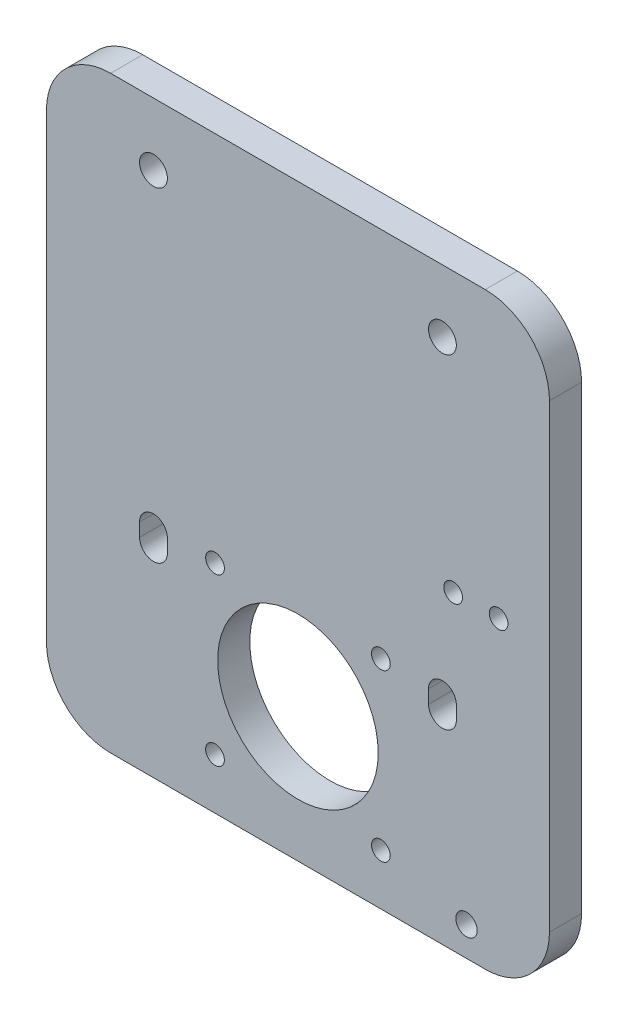
SolidWorks part; units mm, degrees
material "Polycarbonate (PC)"
ref_plane "Спереди" through (0, 0, 0) normal (0, 0, 1) x (1, 0, 0)
ref_plane "Сверху" through (0, 0, 0) normal (0, 1, 0) x (1, 0, 0)
ref_plane "Справа" through (0, 0, 0) normal (1, 0, 0) x (0, 0, -1)
sketch "Model" plane through (0, 0, 0) normal (0, 0, 1) x (1, 0, 0)
  line L4 (-22.7195, 98.3) -> (-31.6357, 98.3) construction
  line L5 (-27, 102.2644) -> (-27, 93.0751) construction
  line L24 (-27, 44.8397) -> (-27, 32.6753) construction
  line L25 (-29.6, 40.1) -> (-29.6, 37.6)
  line L26 (-24.4, 37.6) -> (-24.4, 40.1)
  line L27 (-24.4, 40.1) -> (-24.4, 37.6)
  line L28 (-29.6, 37.6) -> (-29.6, 40.1)
  line L156 (-18.8648, 25) -> (20.0371, 25) construction
  line L159 (27, 44.8397) -> (27, 32.6753) construction
  line L160 (47, 98) -> (47, 12)
  line L165 (27, 102.2644) -> (27, 93.0751) construction
  line L166 (22.7195, 98.3) -> (31.6357, 98.3) construction
  line L167 (35, 0) -> (-35, 0)
  line L174 (-47, 12) -> (-47, 98)
  line L181 (-35, 110) -> (35, 110)
  line L955 (29.6, 37.6) -> (29.6, 40.1)
  line L968 (24.4, 40.1) -> (24.4, 37.6)
  line L1360 (24.4, 37.6) -> (24.4, 40.1)
  line L1373 (29.6, 40.1) -> (29.6, 37.6)
  line L1604 (0, -6.1891) -> (0, 116.9068) construction
  arc A0 (35, 110) -> (47, 98) centre (35, 98) cw
  arc A1 (47, 12) -> (35, 0) centre (35, 12) cw
  arc A2 (-47, 12) -> (-35, 0) centre (-35, 12) ccw
  arc A3 (-47, 98) -> (-35, 110) centre (-35, 98) cw
  circle A8 centre (0, 25) radius 15
  arc A9 (24.4, 40.1) -> (29.6, 40.1) centre (27, 40.1) cw
  arc A10 (24.4, 37.6) -> (29.6, 37.6) centre (27, 37.6) ccw
  circle A19 centre (27, 98.3) radius 2.6
  circle A22 centre (-27, 98.3) radius 2.6
  arc A29 (-24.4, 37.6) -> (-29.6, 37.6) centre (-27, 37.6) cw
  arc A30 (-24.4, 40.1) -> (-29.6, 40.1) centre (-27, 40.1) ccw
  dimension "D1" = 12
  dimension "D12" = 30
  dimension "D15" = 2.6
  dimension "D38" = 5.2
  dimension "D3" = 110
  dimension "D4" = 25
  dimension "D6" = 40.1
  dimension "D7" = 94
  dimension "D8" = 54
  dimension "D13" = 5.2
  dimension "D14" = 2.5
  dimension "D36" = 58.2
extrude "Base" add sketch "Model" along normal blind 6 contours A3 L174 A2 L167 A1 L160 A0 L181 A30 L26 A29 L25 A8 A10 L968 A9 L955 region at (0, 57.1783, 0)
sketch "Sketch2" plane through (0, 0, 6) normal (0, 0, 1) x (1, 0, 0)
  line L0 (35, 0) -> (-35, 0) construction
  line L1 (47, 98) -> (47, 12) construction
  circle A0 centre (31.5, 5.5) radius 2
  dimension "D1" = 4
  dimension "D2" = 5.5
  dimension "D3" = 15.5
extrude "CableTieMount" cut sketch "Sketch2" against normal through all
hole_wizard "Ø3.5 (3.5) StepperMount" positions "Sketch3" profile "Sketch4" hole size "Ø3.5" standard "ANSI Metric" end condition through all
sketch "Sketch3" plane through (0, 0, 6) normal (0, 0, 1) x (1, 0, 0)
  line L0 (0, 0) -> (0, 14.3141) construction
  line L4 (35, 0) -> (-35, 0) construction
  point P0 (-15.5, 40.5)
  point P2 (-15.5, 9.5)
  point P4 (15.5, 9.5)
  point P6 (15.5, 40.5)
  dimension "D1" = 31
  dimension "D2" = 31
  dimension "D3" = 9.5
sketch "Sketch4" plane through (-15.5, 40.5, 6) normal (1, 0, 0) x (0, -1, 0)
  line L0 (0, 0) -> (0, 6)
  line L1 (0, 6) -> (1.75, 6)
  line L2 (1.75, 6) -> (1.75, 0)
  line L5 (1.75, 0) -> (0, 0)
  line L11 (0, -6.35) -> (0, 107.95) construction
  dimension "Thru Hole Dia." = 3.5
  dimension "Thru Hole Depth" = 6
hole_wizard "Ø3.5 (3.5) CableChainMount" positions "Sketch5" profile "Sketch6" hole size "Ø3.5" standard "ANSI Metric" end condition through all
sketch "Sketch5" plane through (0, 0, 0) normal (0, 0, -1) x (-1, 0, 0)
  line L0 (-47, 98) -> (-47, 12) construction
  line L1 (-35, 0) -> (35, 0) construction
  point P0 (-37.5, 58)
  point P2 (-29, 58)
  point P5 (0, 0)
  dimension "D1" = 9.5
  dimension "D2" = 8.5
  dimension "D3" = 58
sketch "Sketch6" plane through (37.5, 58, 0) normal (1, 0, 0) x (0, 1, 0)
  line L0 (0, 0) -> (0, 6)
  line L1 (0, 6) -> (1.75, 6)
  line L2 (1.75, 6) -> (1.75, 0)
  line L5 (1.75, 0) -> (0, 0)
  line L11 (0, -6.35) -> (0, 107.95) construction
  dimension "Thru Hole Dia." = 3.5
  dimension "Thru Hole Depth" = 6
